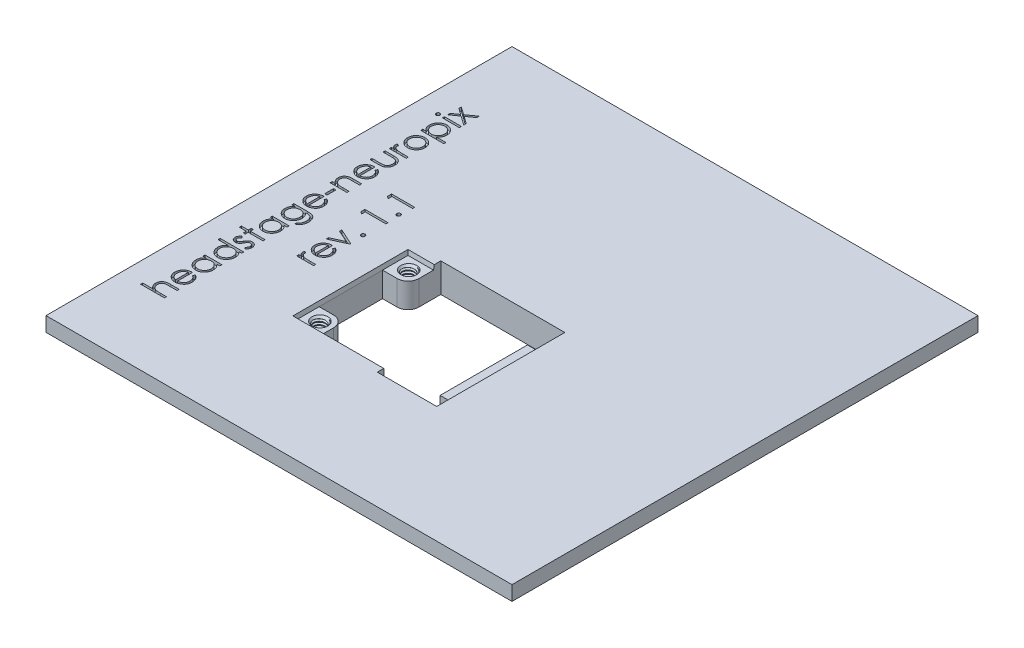
SolidWorks part; units mm, degrees
ref_plane "Front Plane" through (0, 0, 0) normal (0, 0, 1) x (1, 0, 0)
ref_plane "Top Plane" through (0, 0, 0) normal (0, 1, 0) x (1, 0, 0)
ref_plane "Right Plane" through (0, 0, 0) normal (1, 0, 0) x (0, 0, -1)
sketch "Sketch1" plane through (0, 0, 0) normal (0, 1, 0) x (1, 0, 0)
  line L1 (-32, 32) -> (32, 32)
  line L2 (-32, 32) -> (-32, -32)
  line L3 (-32, -32) -> (32, -32)
  line L4 (32, 32) -> (32, -32)
  line L5 (-32, 32) -> (32, -32) construction
  line L6 (-32, -32) -> (32, 32) construction
  point P0 (0, 0)
  dimension "D1" = 64
  dimension "D2" = 64
extrude "Boss-Extrude1" add sketch "Sketch1" along normal blind 4 contours L2 L3 L4 L1
sketch "Sketch2" plane through (0, 0, 0) normal (0, -1, 0) x (1, 0, 0)
  line L1 (-30, 30) -> (30, 30)
  line L2 (-30, 30) -> (-30, -30)
  line L3 (-30, -30) -> (30, -30)
  line L4 (30, 30) -> (30, -30)
  line L5 (-30, 30) -> (30, -30) construction
  line L6 (-30, -30) -> (30, 30) construction
  line L7 (32, 32) -> (-32, 32)
  line L8 (32, 32) -> (32, -32)
  line L9 (32, -32) -> (-32, -32)
  line L10 (-32, 32) -> (-32, -32)
  line L11 (32, 32) -> (-32, -32) construction
  line L12 (32, -32) -> (-32, 32) construction
  point P0 (0, 0)
  point P6 (0, 0)
  line M5 (-32, -32) -> (32, -32)
  line M6 (32, -32) -> (32, 32)
  line M7 (32, 32) -> (-32, 32)
  line M8 (-32, 32) -> (-32, -32)
  dimension "D1" = 2
  dimension "D2" = 2
extrude "Cut-Extrude1" cut sketch "Sketch2" against normal blind 2 contours L1 L4 L3 L2 M8 M5 M6 M7 region at (31.0949, 0, 0)
sketch "Sketch4" plane through (0, 4, 0) normal (0, 1, 0) x (1, 0, 0)
  line L0 (4.3, -7.18) -> (-6.8945, -7.18) construction
  line L1 (-14.9, -14.98) -> (5.3, -14.98)
  line L2 (-14.9, -14.98) -> (-14.9, 0.62)
  line L3 (-14.9, 0.62) -> (5.3, 0.62)
  line L4 (5.3, -14.98) -> (5.3, 0.62)
  point P4 (4.3, -7.18)
  point P6 (0, 0)
  point P8 (-13.1, -1.08)
  point P9 (3.8796, -7.2861)
  point P12 (-13.1, -13.28)
  dimension "D1" = 1
  dimension "D2" = 19.2
  dimension "D3" = 7.8
  dimension "D4" = 7.8
  dimension "D5" = 17.4
  dimension "D6" = 6.1
extrude "Cut-Extrude2" cut sketch "Sketch4" along normal blind 10 draft 10 from offset 0.6 contours L3 L4 L1 L2 draft outward yes offset against normal yes
hole_wizard "Tap Drill for M2x0.4 Tap1" positions "3DSketch1" profile "Sketch5" hole size "M2x0.4" standard "ANSI Metric" end condition through all
sketch3d "3DSketch1"
  point P0 (-13.1, 4, 13.28)
  point P3 (-13.1, 4, 1.08)
sketch "Sketch5" plane through (-13.1, 4, 13.28) normal (1, 0, 0) x (0, 0, 1)
  line L0 (0, 0) -> (0, 4)
  line L1 (0, 4) -> (0.8, 4)
  line L2 (0.8, 4) -> (0.8, 0)
  line L5 (0.8, 0) -> (0, 0)
  line L11 (0, -6.35) -> (0, 107.95) construction
  dimension "Thru Hole Dia." = 1.6
  dimension "Thru Hole Depth" = 4
thread "Thread1" pitch 0.4 method cut profile "Thread Profile1" start angle 0, offset 1, length 0, pitch 0.4, diameter 1.6
ref_plane "Plane1" through (-13.9, 4.4, 1.08) normal (0, 0, 1) x (-1, 0, 0)
sketch "Thread Profile1" plane through (-13.9, 4.4, 1.08) normal (0, 0, 1) x (-1, 0, 0)
  line L0 (0, 0) -> (0, 0.4) construction
  line L1 (0, 0) -> (0.2165, 0.125)
  line L2 (0.2165, 0.125) -> (0.2165, 0.175)
  line L3 (0.2165, 0.175) -> (0, 0.3)
  line L4 (0.2165, 0.15) -> (0, 0.15) construction
  line L11 (0, 0) -> (0, 0.3)
  point P2 (0, 0)
  dimension "Pitch" = 0.4
  dimension "Profile_Angle" = 60
  dimension "Profile_Land" = 0.05
  dimension "Profile_Height" = 0.2165
thread "Thread2" pitch 0.4 method cut profile "Thread Profile2" start angle 0, offset 1, length 0, pitch 0.4, diameter 1.6
ref_plane "Plane2" through (-13.9, 4.4, 13.28) normal (0, 0, 1) x (-1, 0, 0)
sketch "Thread Profile2" plane through (-13.9, 4.4, 13.28) normal (0, 0, 1) x (-1, 0, 0)
  line L0 (0, 0) -> (0, 0.4) construction
  line L1 (0, 0) -> (0.2165, 0.125)
  line L2 (0.2165, 0.125) -> (0.2165, 0.175)
  line L3 (0.2165, 0.175) -> (0, 0.3)
  line L4 (0.2165, 0.15) -> (0, 0.15) construction
  line L11 (0, 0) -> (0, 0.3)
  point P2 (0, 0)
  dimension "Pitch" = 0.4
  dimension "Profile_Angle" = 60
  dimension "Profile_Land" = 0.05
  dimension "Profile_Height" = 0.2165
sketch "Sketch10" plane through (0, 3.4, 0) normal (0, 1, 0) x (1, 0, 0)
  circle A0 centre (-13.1, -13.28) radius 1.1
  circle A1 centre (-13.1, -1.08) radius 1.1
  dimension "D1" = 2.2
  dimension "D2" = 2.2
extrude "Cut-Extrude3" cut sketch "Sketch10" against normal blind 10 draft 45
sketch "Sketch11" plane through (0, 3.4, 0) normal (0, 1, 0) x (1, 0, 0)
  line L0 (-14.9, -11.5858) -> (-12.9, -11.5858)
  line L1 (-14.9, -14.98) -> (-14.9, 0.62) construction
  line L2 (-11.4, -13.0858) -> (-11.4, -14.5858)
  line L3 (-6.5324, -15.0858) -> (-2.5257, -15.0858)
  line L4 (-2.5257, -15.0858) -> (-2.5257, -15.98)
  line L5 (-2.5257, -15.98) -> (5.6369, -15.98)
  line L6 (5.6369, -15.98) -> (5.6369, 1.62)
  line L7 (5.6369, 1.62) -> (-11.4, 1.62)
  line L8 (-11.4, 1.62) -> (-11.4, -1.38)
  line L9 (-12.9, -2.88) -> (-14.9, -2.88)
  line L10 (-14.9, -2.88) -> (-14.9, -11.5858)
  line L11 (-14.9, 0.62) -> (5.3, 0.62) construction
  line L12 (-15.0058, -15.0858) -> (5.4058, -15.0858) construction
  line L13 (-11.4, -14.5858) -> (-6.5324, -14.5858)
  line L14 (-6.5324, -14.5858) -> (-6.5324, -15.0858)
  line L15 (-14.9, -14.98) -> (5.3, -14.98) construction
  arc A0 (-11.4, -13.0858) -> (-12.9, -11.5858) centre (-12.9, -13.0858) ccw
  arc A1 (-11.4, -1.38) -> (-12.9, -2.88) centre (-12.9, -1.38) cw
  point P14 (-11.4, -11.5858)
  dimension "D3" = 1.5
  dimension "D5" = 1.5
  dimension "D1" = 3.5
  dimension "D2" = 1
  dimension "D4" = 3.5
  dimension "D6" = 1
  dimension "D7" = 0.5
extrude "Cut-Extrude4" cut sketch "Sketch11" against normal through all and the other way through all
sketch "Sketch12" plane through (0, 0, 0) normal (0, 1, 0) x (1, 0, 0)
  line L0 (4.3, -7.18) -> (-6.8945, -7.18) construction
  line L1 (3.303, -13.18) -> (6.4277, -13.18)
  line L2 (3.303, -13.18) -> (3.303, -1.18)
  line L3 (3.303, -1.18) -> (6.4277, -1.18)
  line L4 (6.4277, -13.18) -> (6.4277, -1.18)
  point P4 (6.4277, -7.18)
  dimension "D1" = 12
extrude "Boss-Extrude2" add sketch "Sketch12" along normal offset from surface (2.75 mm away) 1.25 up to face at (-5.9024, 4, 8.0584)
sketch "Sketch13" plane through (0, 4, 0) normal (0, 1, 0) x (1, 0, 0)
  line L0 (-25.9753, -25.694) -> (-25.9753, 25.0231) construction
  text T0 "headstage-neuropix\r\nrev. 1.1"
extrude "Cut-Extrude5" cut sketch "Sketch13" against normal blind 0.5
